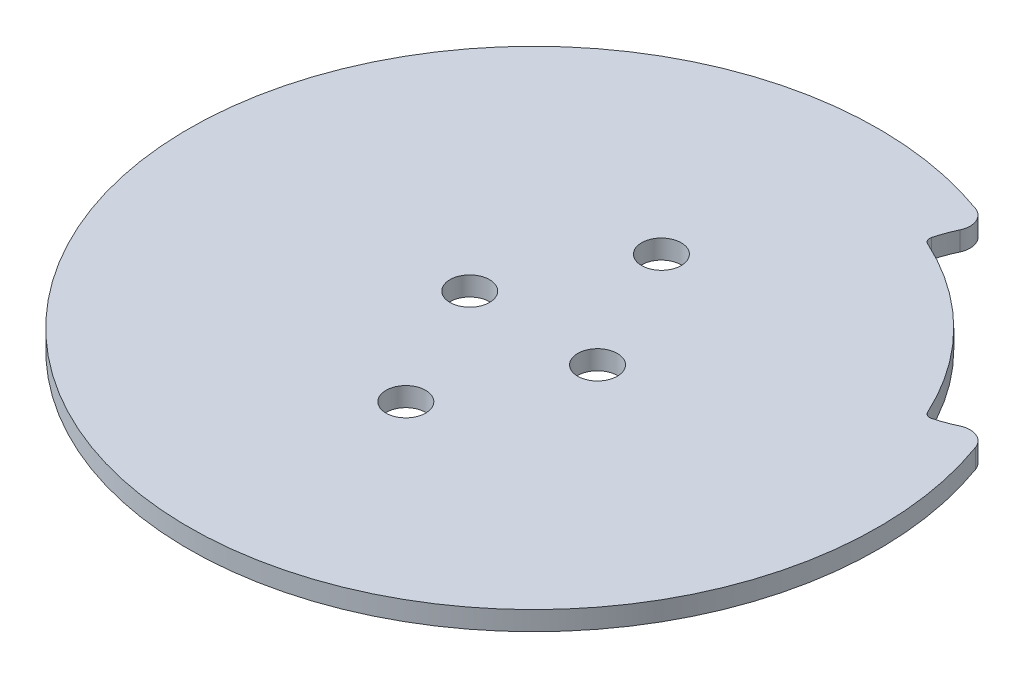
SolidWorks part; units mm, degrees
ref_plane "Front Plane" through (0, 0, 0) normal (0, 0, 1) x (1, 0, 0)
ref_plane "Top Plane" through (0, 0, 0) normal (0, 1, 0) x (1, 0, 0)
ref_plane "Right Plane" through (0, 0, 0) normal (1, 0, 0) x (0, 0, -1)
sketch "Sketch1" plane through (0, 0, 0) normal (0, 1, 0) x (1, 0, 0)
  line L0 (38.1838, 38.1838) -> (0, 0) construction
  line L1 (0, 0) -> (-49.6397, 0) construction
  circle A0 centre (0, 0) radius 54
  circle A1 centre (0, 0) radius 20 construction
  circle A2 centre (0, 20) radius 3.1
  circle A3 centre (0, -20) radius 3.1
  circle A4 centre (-10, 0) radius 3.1
  circle A5 centre (10, 0) radius 3.1
  circle A6 centre (0, 0) radius 10 construction
  circle A7 centre (38.1838, 38.1838) radius 20
  circle A8 centre (0, 0) radius 46.5
  dimension "D1" = 6.2
  dimension "D2" = 40
  dimension "D3" = 108
  dimension "D4" = 20
  dimension "D5" = 6.2
  dimension "D7" = 40
  dimension "D8" = 93
  dimension "D6" = 135
extrude "Boss-Extrude1" add sketch "Sketch1" along normal blind 3 contours A8 A7 A0 | A7 A8 A5 A4 A3 A2 | A7 A8 region at (-43.9213, 0, 28.7106) region at (-1.3309, 0, 1.3309) region at (28.8166, 0, -28.8166)
fillet "Fillet1" radius 3 2 edges at (49.4624, 1.5, -21.6673) (21.6673, 1.5, -49.4624)
fillet "Fillet2" radius 1 2 edges at (42.5855, 1.5, -18.6742) (18.6742, 1.5, -42.5855)
